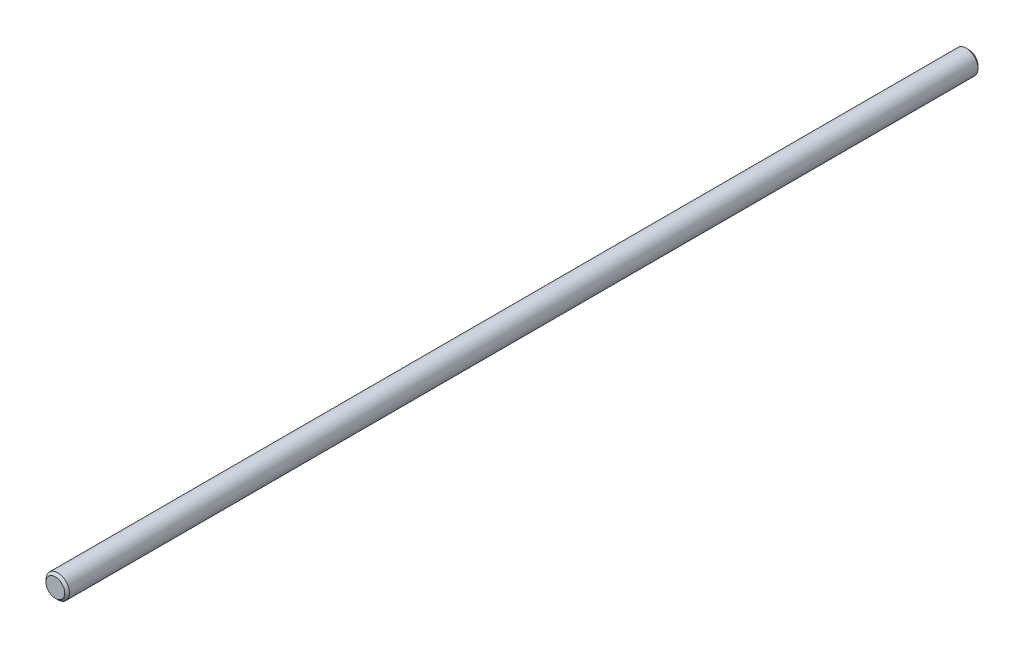
SolidWorks part; units mm, degrees
ref_plane "Piano frontale" through (0, 0, 0) normal (0, 0, 1) x (1, 0, 0)
ref_plane "Piano superiore" through (0, 0, 0) normal (0, 1, 0) x (1, 0, 0)
ref_plane "Piano destro" through (0, 0, 0) normal (1, 0, 0) x (0, 0, -1)
sketch "Schizzo1" plane through (0, 0, 0) normal (0, 0, 1) x (1, 0, 0)
  circle A0 centre (0, 0) radius 5
  dimension "D1" = 10
extrude "Estrusione-Estrusione1" add sketch "Schizzo1" along normal blind 390
chamfer "Smusso1" distance 1 angle 45 2 edges at (5, 0, 390) (5, 0, 0)
